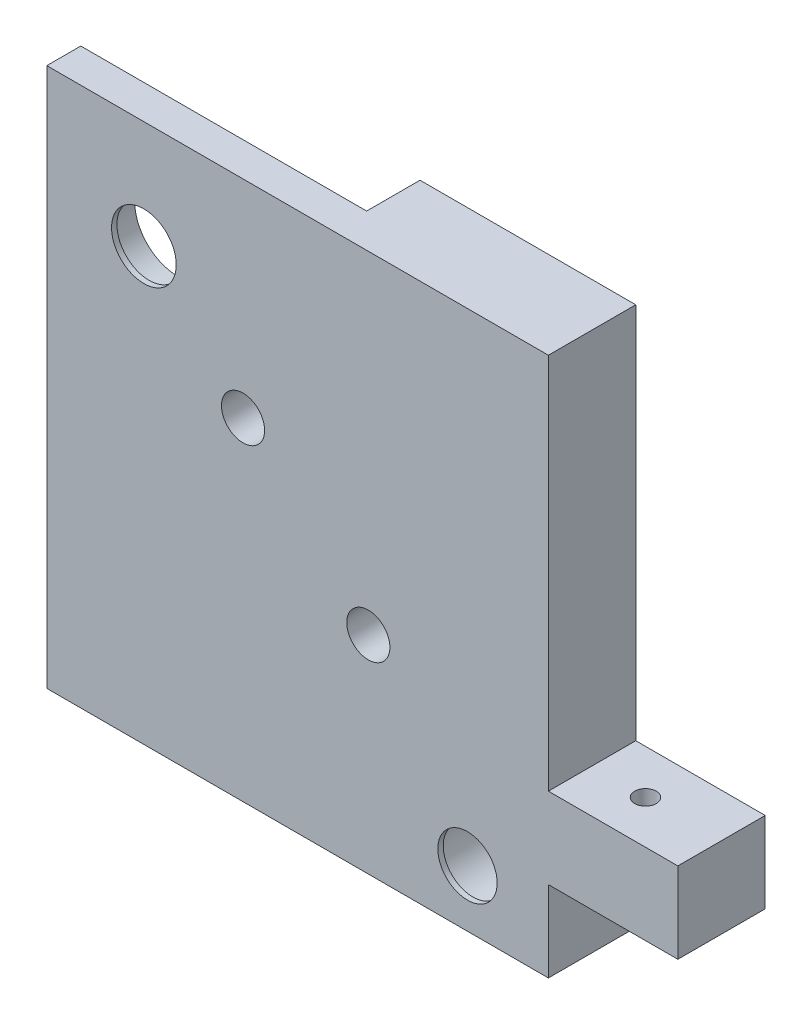
SolidWorks part; units mm, degrees
ref_plane "Front Plane" through (0, 0, 0) normal (0, 0, 1) x (1, 0, 0)
ref_plane "Top Plane" through (0, 0, 0) normal (0, 1, 0) x (1, 0, 0)
ref_plane "Right Plane" through (0, 0, 0) normal (1, 0, 0) x (0, 0, -1)
sketch "Sketch1" plane through (0, 0, 0) normal (0, 0, 1) x (1, 0, 0)
  line L1 (-76.1871, 64.9281) -> (16.8129, 64.9281)
  line L2 (-76.1871, 64.9281) -> (-76.1871, -35.0719)
  line L3 (-76.1871, -35.0719) -> (16.8129, -35.0719)
  line L4 (16.8129, 64.9281) -> (16.8129, -35.0719)
  dimension "D1" = 93
  dimension "D2" = 100
extrude "Boss-Extrude2" add sketch "Sketch1" along normal blind 6.3 contours L1 L4 L3 L2
sketch "Sketch3" plane through (0, 0, 0) normal (0, 0, -1) x (-1, 0, 0)
  line L0 (76.1871, -35.0719) -> (-16.8129, -35.0719) construction
  line L1 (-16.8129, 64.9281) -> (23.1871, 64.9281)
  line L2 (-16.8129, 64.9281) -> (-16.8129, -35.0719)
  line L3 (-16.8129, -35.0719) -> (23.1871, -35.0719)
  line L4 (23.1871, 64.9281) -> (23.1871, -35.0719)
  line L5 (-16.8129, 64.9281) -> (-16.8129, -35.0719) construction
  dimension "D1" = 0
  dimension "D2" = 0
  dimension "D3" = 40
  dimension "D4" = 100
extrude "Boss-Extrude3" add sketch "Sketch3" along normal blind 9.9
sketch "Sketch4" plane through (16.8129, 0, 0) normal (1, 0, 0) x (0, 0, -1)
  line L0 (-6.3, 64.9281) -> (-6.3, -35.0719) construction
  line L1 (-6.3, -5.0719) -> (9.9, -5.0719)
  line L2 (-6.3, -5.0719) -> (-6.3, -20.0719)
  line L3 (-6.3, -20.0719) -> (9.9, -20.0719)
  line L4 (9.9, -5.0719) -> (9.9, -20.0719)
  line L5 (9.9, 64.9281) -> (9.9, -35.0719) construction
  line L6 (-6.3, -35.0719) -> (9.9, -35.0719) construction
  dimension "D1" = 15
  dimension "D2" = 15
extrude "Boss-Extrude4" add sketch "Sketch4" along normal blind 24
sketch "Sketch5" plane through (0, -5.0719, 0) normal (0, 1, 0) x (1, 0, 0)
  line L0 (40.8129, -6.3) -> (16.8129, -6.3) construction
  line L2 (16.8129, 9.9) -> (16.8129, -6.3) construction
  circle A0 centre (26.8129, 1.7) radius 2
  dimension "D2" = 4
  dimension "D3" = 10
  dimension "D1" = 8
extrude "Cut-Extrude1" cut sketch "Sketch5" against normal blind 50
sketch "Sketch6" plane through (0, 0, -9.9) normal (0, 0, -1) x (-1, 0, 0)
  line L0 (-16.8129, -35.0719) -> (23.1871, -35.0719) construction
  line L1 (-16.8129, -20.0719) -> (-16.8129, -35.0719) construction
  circle A0 centre (-1.8129, -24.5719) radius 7.5
  dimension "D1" = 15
  dimension "D2" = 10.5
  dimension "D3" = 15
extrude "Cut-Extrude2" cut sketch "Sketch6" against normal blind 50
sketch "Sketch7" plane through (0, 0, 0) normal (0, 0, -1) x (-1, 0, 0)
  line L0 (76.1871, -35.0719) -> (23.1871, -35.0719) construction
  line L2 (-16.8129, 64.9281) -> (-16.8129, -5.0719) construction
  circle A0 centre (58.1871, 44.9281) radius 8
  dimension "D1" = 16
  dimension "D2" = 80
  dimension "D3" = 75
extrude "Cut-Extrude3" cut sketch "Sketch7" against normal blind 50
extrude "Extrude-Thin1" add sketch "Sketch7<2>" along normal blind 1 from surface thin starting at face at (-50.1871, 44.9281, 6.3) thin type one direction reverse wall 2
sketch "Sketch7<2>" plane through (0, 0, 0) normal (0, 0, -1) x (-1, 0, 0) same geometry as "Sketch7"
extrude "Extrude-Thin2" add sketch "Sketch6<2>" along normal blind 1 from surface thin starting at face at (9.3129, -24.5719, 6.3) thin type one direction reverse wall 2
sketch "Sketch6<2>" plane through (0, 0, -9.9) normal (0, 0, -1) x (-1, 0, 0) same geometry as "Sketch6"
sketch "Sketch8" plane through (0, 0, 6.3) normal (0, 0, 1) x (1, 0, 0)
  line L0 (-58.1871, 44.9281) -> (1.8129, -15.0719)
  line L1 (-39.8023, 26.5433) -> (-39.8023, 63.6954)
  line L2 (-39.8023, 63.6954) -> (-39.8023, 26.5433)
  line L4 (1.8129, -15.0719) -> (1.8129, 44.9281)
  line L5 (1.8129, 44.9281) -> (-58.1871, 44.9281)
  line L6 (-39.8023, 26.5433) -> (-16.5718, 3.3128)
  circle A0 centre (-39.8023, 26.5433) radius 4
  circle A1 centre (-16.5718, 3.3128) radius 4
  circle A2 centre (-39.8023, 26.5433) radius 15.8626
  circle A3 centre (-16.5718, 3.3128) radius 15.8626
  circle A5 centre (-58.1871, 44.9281) radius 12
  circle A9 centre (1.8129, -15.0719) radius 12
  point P6 (-28.1871, 14.9281)
  dimension "D1" = 8
  dimension "D2" = 8
  dimension "D3" = 24
  dimension "D4" = 24
  dimension "D5" = 31.7252
  dimension "D6" = 26
  dimension "D7" = 26
extrude "Cut-Extrude4" cut sketch "Sketch8" against normal blind 20 contours L0 A0 L1 | L0 A0 | L1 A0 L0 | L0 A1 | L0 A1 region at (-40.7967, 28.9441, 6.3) region at (-41.0027, 25.3429, 6.3) region at (-37.8702, 27.3436, 6.3) region at (-15.3714, 4.5133, 6.3) region at (-17.7722, 2.1124, 6.3)
